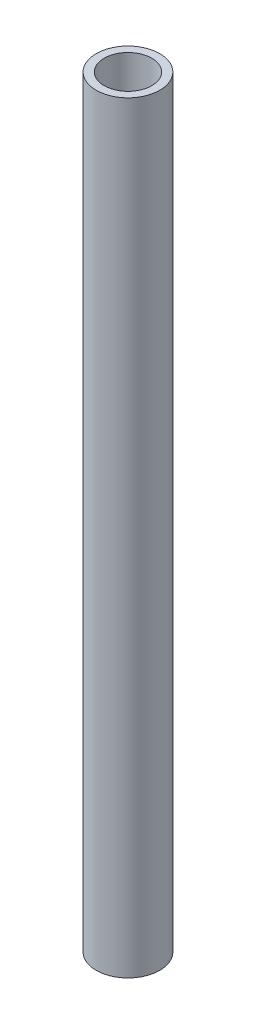
SolidWorks part; units mm, degrees
material "Custom Plastic"
ref_plane "X-Y Datum" through (0, 0, 0) normal (0, 0, 1) x (1, 0, 0)
ref_plane "X-Z Datum" through (0, 0, 0) normal (0, 1, 0) x (1, 0, 0)
ref_plane "Y-Z Datum" through (0, 0, 0) normal (1, 0, 0) x (0, 0, -1)
ref_point "Middle point"
sketch "Sketch2" plane through (0, 0, 0) normal (0, 1, 0) x (1, 0, 0)
  circle A0 centre (0, 0) radius 9.525
  circle A1 centre (0, 0) radius 12.7
  dimension "D1" = 25.4
  dimension "D2" = 19.05
extrude "Tube Stock - Extrude" add sketch "Sketch2" along normal blind 152.4 and the other way blind 152.4
equation "\"Torsion Tube Stock Outer Diameter\"= 1.0in"
equation "\"Torsion Tube Stock Wall Thickness\"= 0.25in"
equation "\"D1@Sketch2\"= \"Torsion Tube Stock Outer Diameter\""
equation "\"D2@Sketch2\"= \"Torsion Tube Stock Outer Diameter\" - \"Torsion Tube Stock Wall Thickness\""
equation "\"Torsion Tube Stock Length\"= 12in"
